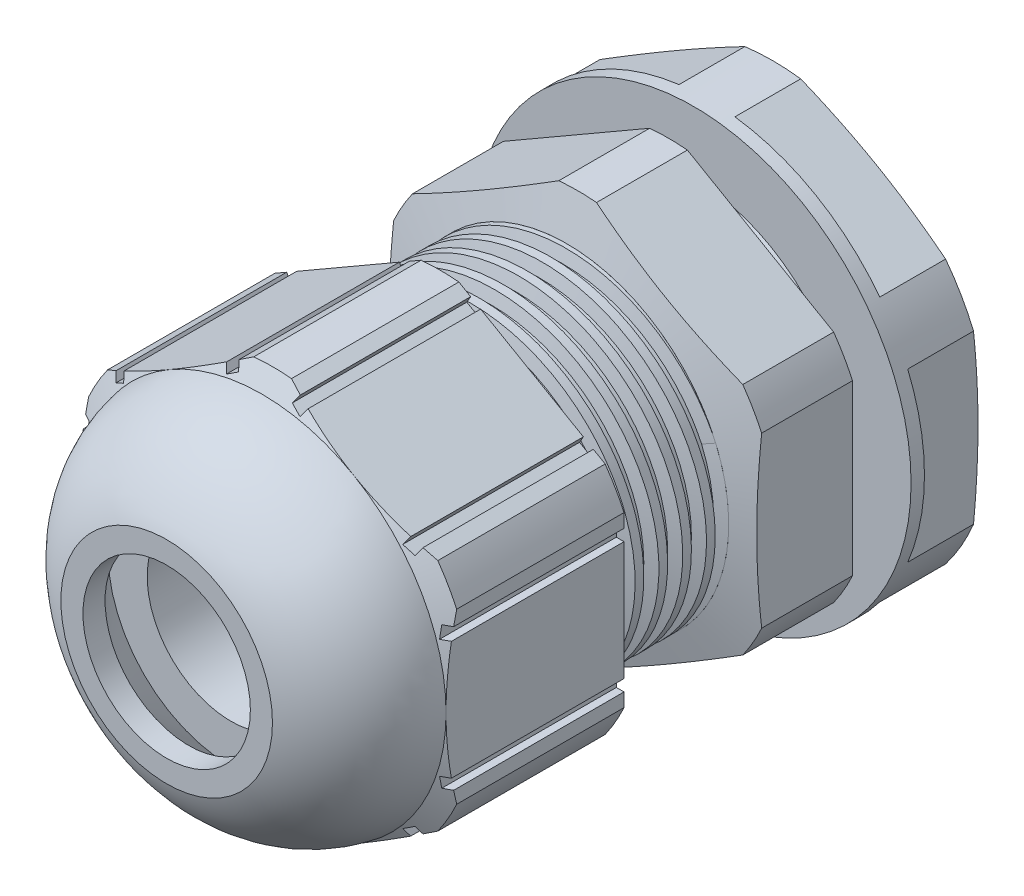
SolidWorks part; units mm, degrees
ref_plane "Front Plane" through (0, 0, 0) normal (0, 0, 1) x (1, 0, 0)
ref_plane "Top Plane" through (0, 0, 0) normal (0, 1, 0) x (1, 0, 0)
ref_plane "Right Plane" through (0, 0, 0) normal (1, 0, 0) x (0, 0, -1)
sketch "Sketch1" plane through (0, 0, 0) normal (1, 0, 0) x (0, 0, -1)
  line L0 (-18.9992, 0) -> (18.9992, 0) construction
  line L1 (-18.9992, 12.1031) -> (-18.9992, -12.1031) construction
  line L2 (18.9992, 9.271) -> (18.9992, -9.271) construction
  line L3 (10.9982, -12.1031) -> (10.9982, 12.1031) construction
  line L4 (0, 5.0038) -> (0, -5.0038) construction
  line L5 (12.4982, -13) -> (12.4982, 13) construction
  point P9 (0, 1.9939)
  point P12 (10.9982, 0)
  point P13 (12.4982, 12)
  point P14 (0, -1.9939)
  point P15 (-18.9992, -11)
  point P16 (-18.9992, 11)
  point P17 (10.9982, -11)
  point P18 (10.9982, 11)
  point P19 (17.5768, 0)
  point P22 (12.4982, 0)
  point P24 (12.4982, -12)
  dimension "C" = 37.9984
  dimension "D" = 8.001
  dimension "For Cord OD [Max]" = 10.0076
  dimension "For Cord OD [Min]" = 3.9878
  dimension "A" = 24.2062
  dimension "SW" = 22
  dimension "D7" = 24.2062
  dimension "D8" = 22
  dimension "Thread OD" = 18.542
  dimension "Thread Pitch" = 1.4224
  dimension "D1" = 1.5
  dimension "A1" = 26
  dimension "SW1" = 24
sketch "Sketch2" plane through (0, 0, 0) normal (1, 0, 0) x (0, 0, -1)
  line L0 (18.9992, 0) -> (18.9992, 9.271)
  line L1 (18.9992, 9.271) -> (10.9982, 9.271)
  line L2 (10.9982, -12.1031) -> (10.9982, 12.1031) construction
  line L3 (10.9982, 0) -> (10.9982, 12.1031)
  line L4 (10.9982, 12.1031) -> (4.9185, 12.1031)
  line L5 (4.9185, 12.1031) -> (4.9185, 0)
  line L6 (-18.9992, 0) -> (18.9992, 0) construction
  line L7 (4.9185, 9.68) -> (-12.6394, 9.68)
  line L8 (-2.6599, 12.1031) -> (-2.6599, 0)
  line L9 (-2.6599, 12.1031) -> (-13.2994, 12.1031)
  line L10 (-13.2994, 12.1031) -> (-13.2994, 0)
  line L11 (-18.9992, 0) -> (-18.9992, 6.3238)
  line L12 (-18.9992, 12.1031) -> (-18.9992, -12.1031) construction
  line L13 (10.9982, 11) -> (4.9185, 11)
  line L14 (-13.2994, 11) -> (-2.6599, 11)
  line L15 (-12.6394, 9.68) -> (-12.6394, 0)
  line L16 (-18.9992, 5.0038) -> (18.9992, 5.0038)
  line L17 (-18.9992, 0) -> (18.9992, 0) construction
  line L18 (12.4982, 9.271) -> (12.4982, 13)
  line L19 (12.4982, 13) -> (17.4982, 13)
  line L20 (17.4982, 13) -> (17.4982, 9.271)
  line L21 (13.2982, 13) -> (13.2982, 9.271)
  line L22 (13.2982, 12) -> (17.4982, 12)
  line L23 (-3.9799, 5.0038) -> (-3.9799, 7.3419)
  line L24 (-3.9799, 7.3419) -> (-15.1593, 7.3419)
  line L25 (-15.1593, 7.3419) -> (-15.1593, 5.0038)
  line L26 (18.9992, 6.6396) -> (-3.9799, 5.0038)
  line L27 (-12.6394, 9.68) -> (-17.6792, 5.0038)
  line L28 (18.0035, 9.271) -> (18.9992, 8.2753)
  line L29 (18.9992, 8.2753) -> (10.9982, 8.2753) construction
  line L30 (-3.9799, 7.3419) -> (-3.9799, 9.68) construction
  line L31 (14.9987, 8.2753) -> (14.9987, 6.6396) construction
  line L32 (14.9987, 6.6396) -> (14.9987, 5.0038) construction
  line L33 (-9.5696, 7.3419) -> (-9.5696, 9.68)
  line L34 (-13.2994, 11) -> (-17.465, 10.2655) construction
  line L35 (-17.465, 10.2655) -> (-18.9992, 6.3238) construction
  arc A0 (-18.9992, 6.3238) -> (-13.2994, 11) centre (-11.9941, 3.5972) cw
  dimension "B1" = 5
  dimension "C1" = 0.8
  dimension "D1" = 45
  dimension "D3" = 0.9957
  dimension "D4" = 6.0797
  dimension "D2" = 16.3393
  dimension "D5" = 10.6396
  dimension "D6" = 1.32
  dimension "D7" = 1.32
  dimension "D9" = 1.32
  dimension "D11" = 1.32
  dimension "D8" = 0.66
  dimension "D12" = 14.4881
  dimension "D10" = 10
sketch "Sketch4" plane through (0, 0, 0) normal (1, 0, 0) x (0, 0, -1)
  line L1 (-2.6599, 12.1031) -> (-2.6599, 0) construction
  line L2 (-2.6599, 12.1031) -> (-13.2994, 12.1031) construction
  line L4 (-18.9992, 0) -> (-18.9992, 6.3238) construction
  line L6 (-2.6599, 12.1031) -> (-2.6599, 9.68)
  line L7 (-2.6599, 12.1031) -> (-12.6626, 12.1031)
  line L9 (-18.9992, 5.0038) -> (-18.9992, 6.3238)
  line L10 (-13.2994, 11) -> (-12.6626, 12.1031)
  line L11 (-13.2994, 12.1031) -> (-13.2994, 0) construction
  line L13 (4.9185, 9.68) -> (-12.6394, 9.68) construction
  line L16 (-2.6599, 9.68) -> (-12.6394, 9.68)
  line L18 (-12.6394, 9.68) -> (-17.6792, 5.0038) construction
  line L19 (-12.6394, 9.68) -> (-17.6792, 5.0038)
  line L20 (-18.9992, 5.0038) -> (18.9992, 5.0038) construction
  line L21 (-18.9992, 5.0038) -> (-17.6792, 5.0038)
  arc A0 (-13.2994, 11) -> (-18.9992, 6.3238) centre (-11.9941, 3.5972) ccw construction
  arc A1 (-13.2994, 11) -> (-18.9992, 6.3238) centre (-11.9941, 3.5972) ccw
  dimension "D1" = 30
revolve "Revolve1" add sketch "Sketch4" angle 360 about L17
sketch "Sketch6" plane through (0, 0, 2.6599) normal (0, 0, -1) x (-1, 0, 0)
  line L1 (0, 12.7017) -> (-11, 6.3509)
  line L2 (-11, 6.3509) -> (-11, -6.3509)
  line L3 (-11, -6.3509) -> (0, -12.7017)
  line L4 (0, -12.7017) -> (11, -6.3509)
  line L5 (11, -6.3509) -> (11, 6.3509)
  line L6 (11, 6.3509) -> (0, 12.7017)
  circle A0 centre (0, 0) radius 11 construction
extrude "Cut-Extrude1" cut sketch "Sketch6" against normal through all flip side to cut
sketch "Sketch12" plane through (0, 0, 2.6599) normal (0, 0, -1) x (-1, 0, 0)
  line L0 (0, 12.7017) -> (0, 0) construction
  line L1 (1.8333, 11.6432) -> (1.6034, 11.245)
  line L2 (2.132, 11.4708) -> (2.0171, 11.2716) construction
  line L3 (2.0171, 11.2716) -> (1.9021, 11.0725) construction
  line L4 (11, 6.3509) -> (0, 12.7017) construction
  line L5 (1.6034, 11.245) -> (2.2008, 10.9)
  line L6 (2.2008, 10.9) -> (2.4307, 11.2983)
  line L7 (2.4307, 11.2983) -> (1.8333, 11.6432)
  line L8 (0, 12.7017) -> (1.8333, 11.6432) construction
  line L9 (1.8333, 11.6432) -> (3.6667, 10.5848) construction
  line L10 (3.6667, 10.5848) -> (5.5, 9.5263) construction
  line L11 (1.7184, 11.4441) -> (1.9175, 11.3291) construction
  line L12 (1.9175, 11.3291) -> (2.1166, 11.2141) construction
  line L13 (2.1166, 11.2141) -> (2.3158, 11.0992) construction
  line L14 (-2.4307, 11.2983) -> (-1.8333, 11.6432)
  line L15 (-2.2008, 10.9) -> (-2.4307, 11.2983)
  line L16 (-1.6034, 11.245) -> (-2.2008, 10.9)
  line L17 (-1.8333, 11.6432) -> (-1.6034, 11.245)
  circle A4 centre (0, 0) radius 11.12
  circle A5 centre (0, 0) radius 11.12 construction
  dimension "D1" = 0.12
extrude "Cut-Extrude4" cut sketch "Sketch12" against normal through all
pattern_circular "CirPattern1" count 6 over 360 about axis through (0, 0, 18.9992) along (0, 0, -1) of "Cut-Extrude4" reverse direction yes
sketch "Sketch5" plane through (0, 0, 0) normal (1, 0, 0) x (0, 0, -1)
  line L1 (18.9992, 0) -> (18.9992, 9.271) construction
  line L2 (18.9992, 9.271) -> (10.9982, 9.271) construction
  line L3 (10.9982, 0) -> (10.9982, 12.1031) construction
  line L4 (10.9982, 12.1031) -> (4.9185, 12.1031) construction
  line L5 (4.9185, 12.1031) -> (4.9185, 0) construction
  line L6 (4.9185, 9.68) -> (-12.6394, 9.68) construction
  line L9 (18.9992, 6.6396) -> (18.9992, 8.2753)
  line L10 (18.0035, 9.271) -> (10.9982, 9.271)
  line L11 (10.9982, 9.271) -> (10.9982, 12.1031)
  line L12 (10.9982, 12.1031) -> (5.5677, 12.1031)
  line L14 (4.9185, 9.68) -> (-9.5696, 9.68)
  line L16 (4.9185, 9.68) -> (5.5677, 12.1031)
  line L18 (18.9992, 6.6396) -> (-3.9799, 5.0038) construction
  line L19 (18.9992, 6.6396) -> (-3.9799, 5.0038)
  line L20 (-3.9799, 5.0038) -> (-3.9799, 7.3419) construction
  line L21 (-3.9799, 7.3419) -> (-15.1593, 7.3419) construction
  line L22 (-3.9799, 5.0038) -> (-3.9799, 7.3419)
  line L23 (-3.9799, 7.3419) -> (-9.5696, 7.3419)
  line L24 (18.0035, 9.271) -> (18.9992, 8.2753) construction
  line L25 (18.0035, 9.271) -> (18.9992, 8.2753)
  line L26 (-9.5696, 7.3419) -> (-9.5696, 9.68) construction
  line L27 (-9.5696, 7.3419) -> (-9.5696, 9.68)
  dimension "D1" = 15
revolve "Revolve2" add sketch "Sketch5" angle 360 about L17
sketch "Sketch7" plane through (0, 0, -10.9982) normal (0, 0, 1) x (1, 0, 0)
  line L1 (0, 12.7017) -> (-11, 6.3509)
  line L2 (-11, 6.3509) -> (-11, -6.3509)
  line L3 (-11, -6.3509) -> (0, -12.7017)
  line L4 (0, -12.7017) -> (11, -6.3509)
  line L5 (11, -6.3509) -> (11, 6.3509)
  line L6 (11, 6.3509) -> (0, 12.7017)
  circle A0 centre (0, 0) radius 11 construction
extrude "Cut-Extrude2" cut sketch "Sketch7" along normal through all flip side to cut
sketch "Sketch8" plane through (0, 0, 0) normal (1, 0, 0) x (0, 0, -1)
  line L0 (-18.9992, 5.0038) -> (18.9992, 5.0038) construction
  line L1 (-3.9799, 5.0038) -> (-3.9799, 7.3419) construction
  line L2 (-3.9799, 7.3419) -> (-15.1593, 7.3419) construction
  line L3 (-15.1593, 7.3419) -> (-15.1593, 5.0038) construction
  line L4 (-15.1593, 5.0038) -> (-3.9799, 5.0038)
  line L5 (-3.9799, 5.0038) -> (-3.9799, 7.3419)
  line L6 (-3.9799, 7.3419) -> (-15.1593, 7.3419)
  line L7 (-15.1593, 7.3419) -> (-15.1593, 5.0038)
revolve "Revolve3" add sketch "Sketch8" angle 360 about L17
sketch "Sketch9" plane through (0, 0, 0) normal (1, 0, 0) x (0, 0, -1)
  line L0 (18.9992, 9.271) -> (10.9982, 9.271) construction
  line L1 (17.4982, 13) -> (17.4982, 9.271) construction
  line L2 (12.4982, 13) -> (17.4982, 13) construction
  line L3 (12.4982, 9.271) -> (12.4982, 13) construction
  line L4 (17.4982, 9.271) -> (12.4982, 9.271)
  line L5 (17.4982, 12) -> (17.4982, 9.271)
  line L6 (12.4982, 13) -> (17.2303, 13)
  line L7 (12.4982, 9.271) -> (12.4982, 13)
  line L8 (17.4982, 12) -> (17.2303, 13)
  dimension "D1" = 15
revolve "Revolve4" add sketch "Sketch9" angle 360 about L17
sketch "Sketch10" plane through (0, 0, -17.4982) normal (0, 0, -1) x (-1, 0, 0)
  line L1 (0, 13.8564) -> (-12, 6.9282)
  line L2 (-12, 6.9282) -> (-12, -6.9282)
  line L3 (-12, -6.9282) -> (0, -13.8564)
  line L4 (0, -13.8564) -> (12, -6.9282)
  line L5 (12, -6.9282) -> (12, 6.9282)
  line L6 (12, 6.9282) -> (0, 13.8564)
  circle A0 centre (0, 0) radius 12 construction
extrude "Cut-Extrude3" cut sketch "Sketch10" against normal up to vertex (4.2 mm away) flip side to cut up to point (0, 12, -13.2982)
sketch "Sketch13" plane through (0, 0, 0) normal (1, 0, 0) x (0, 0, -1)
  line L0 (10.9982, 9.271) -> (10.9982, -9.271)
  line L1 (4.9185, 9.68) -> (4.9185, -9.68)
  line L2 (-18.9992, 0) -> (18.9992, 0) construction
  point P6 (4.9185, 0)
  point P7 (10.9982, 0)
split "Split1" trim tools "Sketch13" bodies to split 107 resulting bodies 114 115 116
sketch "Sketch14" plane through (0, 0, -18.9992) normal (0, 0, -1) x (-1, 0, 0)
  circle A0 centre (0, 0) radius 9.271
curve "Helix/Spiral1" pitch 1.4224 height 9.4234 radius 9.271 centre (0, 0, -18.9992) axis (0, 0, 1) start towards (0, 1, 0)
sketch "Sketch15" plane through (0, 0, 0) normal (1, 0, 0) x (0, 0, -1)
  line L0 (18.9103, 9.3769) -> (19.6215, 8.5294) construction
  line L1 (19.6215, 8.5294) -> (20.3327, 9.3769) construction
  line L2 (20.3327, 9.3769) -> (18.9103, 9.3769) construction
  line L3 (18.9992, 9.271) -> (20.2438, 9.271) construction
  line L4 (19.6215, 9.3769) -> (19.6215, 9.271) construction
  line L5 (19.6215, 9.271) -> (19.6215, 8.6353) construction
  line L6 (19.6215, 8.6353) -> (19.6215, 8.5294) construction
  line L7 (19.5326, 8.6353) -> (19.7104, 8.6353)
  line L8 (18.9548, 9.324) -> (20.2883, 9.324)
  line L9 (19.7104, 8.6353) -> (20.2883, 9.324)
  line L10 (19.5326, 8.6353) -> (18.9548, 9.324)
  point P12 (19.6215, 9.324)
  dimension "D1" = 1.4224
  dimension "D2" = 0.1778
  dimension "D3" = 80
sweep "Cut-Sweep1" cut profiles "Sketch15" path "Helix/Spiral1" align with end faces yes
sketch "Sketch23" plane through (0, 0, -10.9982) normal (0, 0, -1) x (-1, 0, 0)
  circle A0 centre (0, 0) radius 6.07 construction
  circle A1 centre (0, 0) radius 6.07
  circle A3 centre (0, 0) radius 9.271
  circle A4 centre (0, 0) radius 9.271
  dimension "D1" = 0
extrude "Boss-Extrude2" add sketch "Sketch23" along normal through all draft 80
sketch "Sketch16" plane through (0, 0, 9.5696) normal (0, 0, 1) x (1, 0, 0)
  circle A0 centre (0, 0) radius 9.68
curve "Helix/Spiral2" pitch 1.4224 height 15.9105 radius 9.68 centre (0, 0, 9.5696) axis (0, 0, -1) start towards (0, 1, 0)
sketch "Sketch17" plane through (0, 0, 0) normal (1, 0, 0) x (0, 0, -1)
  line L0 (-10.7317, 10.6515) -> (-10.0205, 7.9973) construction
  line L1 (-10.0205, 7.9973) -> (-9.3093, 10.6515) construction
  line L2 (-9.3093, 10.6515) -> (-10.7317, 10.6515) construction
  line L3 (-10.0205, 7.9973) -> (-10.0205, 8.483) construction
  line L4 (-10.0205, 10.6515) -> (-10.0205, 10.1658) construction
  line L5 (-10.6015, 10.1658) -> (-9.4394, 10.1658)
  line L6 (-9.7602, 8.9688) -> (-9.4394, 10.1658)
  line L7 (-10.2808, 8.9688) -> (-9.7602, 8.9688)
  line L8 (-10.6015, 10.1658) -> (-10.2808, 8.9688)
  line L9 (-10.4714, 9.68) -> (-9.5696, 9.68) construction
  line L11 (-10.0205, 8.483) -> (-10.0205, 8.9688) construction
  line L12 (-10.0205, 9.68) -> (-10.0205, 10.1658) construction
  dimension "D1" = 30
  dimension "D2" = 1.4224
  dimension "D3" = 0.7112
sweep "Cut-Sweep2" cut profiles "Sketch17" path "Helix/Spiral2" align with end faces yes
sketch "Sketch19" plane through (0, 0, -4.9185) normal (0, 0, 1) x (1, 0, 0)
  circle A0 centre (0, 0) radius 5.6372 construction
  circle A1 centre (0, 0) radius 9.68
  circle A2 centre (0, 0) radius 9.68
  circle A3 centre (0, 0) radius 5.6372
  dimension "D1" = 0
extrude "Boss-Extrude1" add sketch "Sketch19" along normal through all draft 75
sketch "Sketch21" plane through (0, 0, -18.9992) normal (0, 0, -1) x (-1, 0, 0)
  line L0 (0, 9.271) -> (0, -9.271) construction
  line L1 (0, 0) -> (-4.6355, -8.0289) construction
  circle A1 centre (0, 0) radius 9.271
  circle A2 centre (0, 0) radius 9.271 construction
  dimension "D2" = 30
  dimension "D1" = 0
equation "\"D7@Sketch1\" = \"A@Sketch1\""
equation "\"D8@Sketch1\" = \"SW@Sketch1\""
equation "\"D3@Sketch2\" = \"Thread Pitch@Sketch1\" * 0.7"
equation "\"D4@Helix/Spiral1\" = \"Thread Pitch@Sketch1\""
equation "\"D3@Helix/Spiral1\"=\"D@Sketch1\"+\"Thread Pitch@Sketch1\""
equation "\"D2@Sketch15\"=\"D1@Sketch15\"/8"
equation "\"D1@Sketch15\" = \"Thread Pitch@Sketch1\""
equation "\"D4@Helix/Spiral2\" = \"Thread Pitch@Sketch1\""
equation "\"D3@Helix/Spiral2\" = \"D12@Sketch2\" + \"Thread Pitch@Sketch1\""
equation "\"D3@Sketch17\" = \"D2@Sketch17\" / 2"
equation "\"D2@Sketch17\" = \"Thread Pitch@Sketch1\""
equation "\"D7@Sketch2\"=\"D6@Sketch2\""
equation "\"D9@Sketch2\"=\"D6@Sketch2\""
equation "\"D11@Sketch2\"=\"D6@Sketch2\""
equation "\"D2@Sketch2\"=\"C@Sketch1\"*0.43"
equation "\"D5@Sketch2\"=\"C@Sketch1\"*0.28"
equation "\"D4@Sketch2\"=\"C@Sketch1\"*0.16"
equation "\"D6@Sketch2\"=\"SW@Sketch1\"*0.06"
equation "\"D8@Sketch2\"=\"D6@Sketch2\"*0.5"
